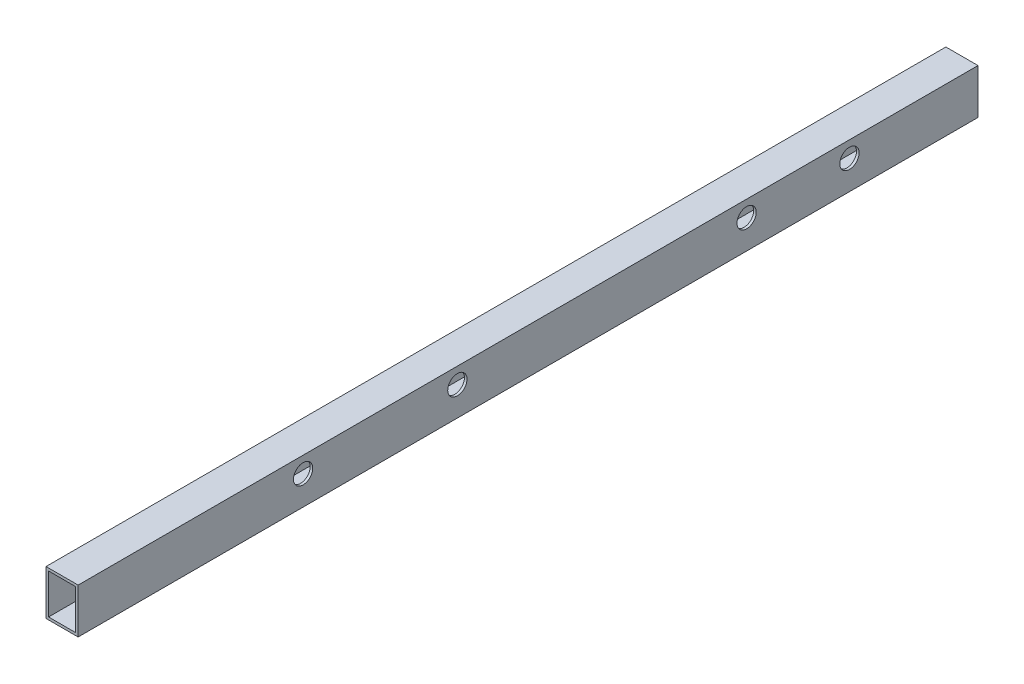
SolidWorks part; units mm, degrees
ref_plane "Front Plane" through (0, 0, 0) normal (0, 0, 1) x (1, 0, 0)
ref_plane "Top Plane" through (0, 0, 0) normal (0, 1, 0) x (1, 0, 0)
ref_plane "Right Plane" through (0, 0, 0) normal (1, 0, 0) x (0, 0, -1)
sketch "Sketch1" plane through (0, 0, 0) normal (0, 0, 1) x (1, 0, 0)
  line L1 (0, 0) -> (50, 0)
  line L2 (0, 0) -> (0, -70)
  line L3 (0, -70) -> (50, -70)
  line L4 (50, 0) -> (50, -70)
  line L5 (4, -4) -> (46, -4)
  line L6 (4, -4) -> (4, -66)
  line L7 (4, -66) -> (46, -66)
  line L8 (46, -4) -> (46, -66)
  dimension "D1" = 70
  dimension "D2" = 50
  dimension "D3" = 4
  dimension "D4" = 4
  dimension "D5" = 4
  dimension "D6" = 4
extrude "Boss-Extrude2" add sketch "Sketch1" along normal blind 1400
sketch "Sketch2" plane through (50, 0, 0) normal (1, 0, 0) x (0, 0, -1)
  line L0 (-1400, -70) -> (-1400, 0) construction
  line L1 (-1400, 0) -> (0, 0) construction
  circle A0 centre (-1050, -25) radius 15
  circle A1 centre (-200, -25) radius 15
  circle A2 centre (-810, -25) radius 15
  circle A3 centre (-360, -25) radius 15
  dimension "D1" = 30
  dimension "D2" = 30
  dimension "D3" = 30
  dimension "D4" = 30
  dimension "D5" = 350
  dimension "D6" = 240
  dimension "D7" = 450
  dimension "D8" = 160
  dimension "D9" = 25
extrude "Cut-Extrude1" cut sketch "Sketch2" against normal through all
equation "\"D4@Sketch1\"=\"D3@Sketch1\""
equation "\"D5@Sketch1\"=\"D3@Sketch1\""
equation "\"D2@Sketch2\"=\"D1@Sketch2\""
